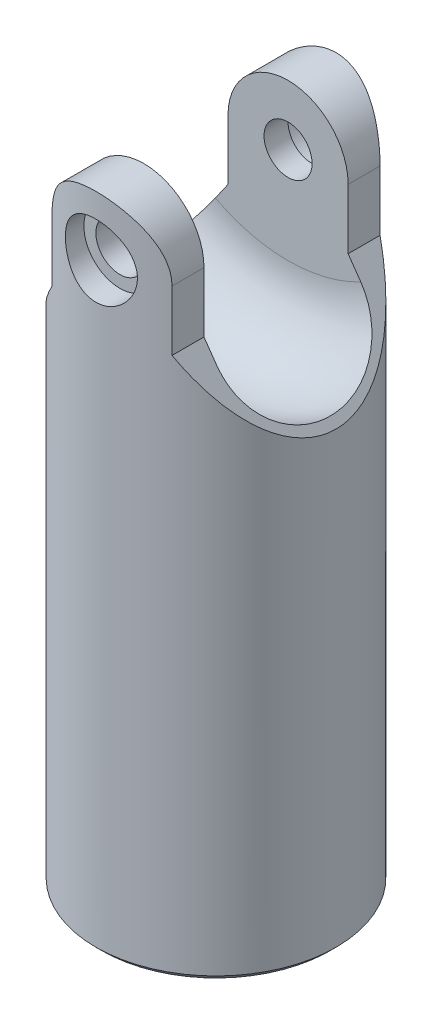
SolidWorks part; units mm, degrees
ref_plane "Alzado" through (0, 0, 0) normal (0, 0, 1) x (1, 0, 0)
ref_plane "Planta" through (0, 0, 0) normal (0, 1, 0) x (1, 0, 0)
ref_plane "Vista lateral" through (0, 0, 0) normal (1, 0, 0) x (0, 0, -1)
sketch "Croquis1" plane through (0, 0, 0) normal (0, 1, 0) x (1, 0, 0)
  circle A0 centre (0, 0) radius 20
  dimension "D1" = 40
extrude "Saliente-Extruir1" add sketch "Croquis1" along normal blind 110
sketch "Croquis2" plane through (0, 0, 0) normal (0, 0, 1) x (1, 0, 0)
  line L0 (-10, 100) -> (-10, 90)
  line L1 (-10, 90) -> (-20, 75.7185)
  line L2 (-20, 110) -> (-20, 0) construction
  line L3 (10, 100) -> (10, 90)
  line L4 (10, 90) -> (20, 75.7185)
  line L5 (20, 0) -> (20, 110) construction
  line L6 (-20, 75.7185) -> (-20, 110)
  line L7 (-20, 110) -> (20, 110)
  line L8 (20, 110) -> (20, 75.7185)
  arc A0 (10, 100) -> (-10, 100) centre (0, 100) ccw
  point P16 (0, 0)
  point P18 (0, 0)
  dimension "D1" = 10
  dimension "D2" = 10
  dimension "D3" = 145
  dimension "D4" = 145
extrude "Cortar-Extruir1" cut sketch "Croquis2" against normal blind 110 and the other way blind 110 contours A0 L7 L6 L1 L0 | A0 L3 L4 L8 L7 region at (14.8763, 96.9702, 0) region at (-14.8763, 96.9702, 0)
sketch "Croquis4" plane through (0, 0, 0) normal (0, 0, 1) x (1, 0, 0)
  circle A0 centre (0, 100) radius 4
  dimension "D1" = 8
extrude "Cortar-Extruir2" cut sketch "Croquis4" against normal blind 110 and the other way blind 110
sketch "Croquis3" plane through (0, 0, 0) normal (1, 0, 0) x (0, 0, -1)
  line L0 (20, 110) -> (-20, 110) construction
  line L1 (-12, 110) -> (12, 110)
  line L2 (-12, 110) -> (-12, 84)
  line L3 (-20, 104) -> (-20, 96) construction
  line L4 (12, 110) -> (12, 84)
  line L5 (0, 0) -> (0, 84) construction
  line L6 (-20, 0) -> (20, 0) construction
  line L7 (-20, 100) -> (19.5959, 100) construction
  line L8 (0, 84) -> (0, 110) construction
  arc A0 (-12, 84) -> (12, 84) centre (0, 84) ccw
  spline S1 degree 2 poles (-20, 104) (-19.2, 100) (-20, 96) knots 0 0 0 1 1 1 weights 0.016 0.02 0.024 construction
  spline S3 degree 2 poles (-20, 104) (-19.2, 100) (-20, 96) knots 0 0 0 1 1 1 weights 0.016 0.02 0.024 construction
  spline S4 degree 2 poles (20, 96) (19.2, 100) (20, 104) knots 0 0 0 1 1 1 weights 0.016 0.02 0.024 construction
  dimension "D2" = 16
  dimension "D3" = 12
  dimension "D1" = 24
revolve "Cortar-Revolución1" cut sketch "Croquis3" angle 360 about L1
ref_plane "Plano1" through (0, 0, 20) normal (0, 0, 1) x (1, 0, 0)
sketch "Croquis5" plane through (0, 0, 20) normal (0, 0, 1) x (1, 0, 0)
  circle A0 centre (0, 100) radius 6
  dimension "D1" = 12
extrude "Cortar-Extruir4" cut sketch "Croquis5" against normal blind 4
mirror "Simetría1" about plane through (0, 0, 0) normal (0, 0, 1) of "Cortar-Extruir4"
sketch "Croquis6" plane through (0, 0, 0) normal (0, 0, 1) x (1, 0, 0)
  line L0 (-20, 0) -> (20, 0) construction
  line L1 (-9, 0) -> (0, 0)
  line L2 (-9, 0) -> (-9, 30)
  line L3 (0, 70) -> (0, 0) construction
  line L4 (0, 70) -> (0, 0)
  line L5 (-9, 30) -> (-14, 30)
  line L8 (0, 70) -> (-14, 70)
  line L9 (-14, 30) -> (-14, 70)
  circle A0 centre (0, 100) radius 4 construction
  dimension "D1" = 28
  dimension "D2" = 40
  dimension "D3" = 30
  dimension "D5" = 9
revolve "Cortar-Revolución2" cut sketch "Croquis6" angle 360 about L3
sketch "Croquis7" plane through (0, 0, 0) normal (0, -1, 0) x (1, 0, 0)
  line L0 (-9.2393, 3.8271) -> (-8.3149, 3.4442)
  line L1 (-10.195, 10.195) -> (0, 0) construction
  line L2 (-3.8271, 9.2393) -> (-3.4442, 8.3149)
  line L3 (0, 0) -> (-12.8654, 0) construction
  line L4 (0, 0) -> (0, 10.0006) construction
  line L5 (3.8271, 9.2393) -> (3.4442, 8.3149)
  line L6 (9.2393, 3.8271) -> (8.3149, 3.4442)
  line L7 (-9.2393, -3.8271) -> (-8.3149, -3.4442)
  line L8 (-3.8271, -9.2393) -> (-3.4442, -8.3149)
  line L9 (9.2393, -3.8271) -> (8.3149, -3.4442)
  line L10 (3.8271, -9.2393) -> (3.4442, -8.3149)
  arc A0 (-3.8271, 9.2393) -> (-9.2393, 3.8271) centre (0, 0) ccw
  circle A1 centre (0, 0) radius 9 construction
  arc A2 (-8.3149, 3.4442) -> (-8.3149, -3.4442) centre (0, 0) ccw
  arc A3 (8.3149, 3.4442) -> (8.3149, -3.4442) centre (0, 0) cw
  arc A4 (3.4442, 8.3149) -> (-3.4442, 8.3149) centre (0, 0) ccw
  arc A5 (-3.8271, -9.2393) -> (-9.2393, -3.8271) centre (0, 0) cw
  arc A6 (3.8271, 9.2393) -> (9.2393, 3.8271) centre (0, 0) cw
  arc A8 (3.4442, -8.3149) -> (-3.4442, -8.3149) centre (0, 0) cw
  arc A9 (3.8271, -9.2393) -> (9.2393, -3.8271) centre (0, 0) ccw
  dimension "D4" = 20.0012
  dimension "D1" = 45
  dimension "D2" = 22.5
  dimension "D3" = 45
extrude "Cortar-Extruir5" cut sketch "Croquis7" against normal blind 44
chamfer "Chaflán1" distance 1 angle 45 1 edges at (0, 0, 20)
